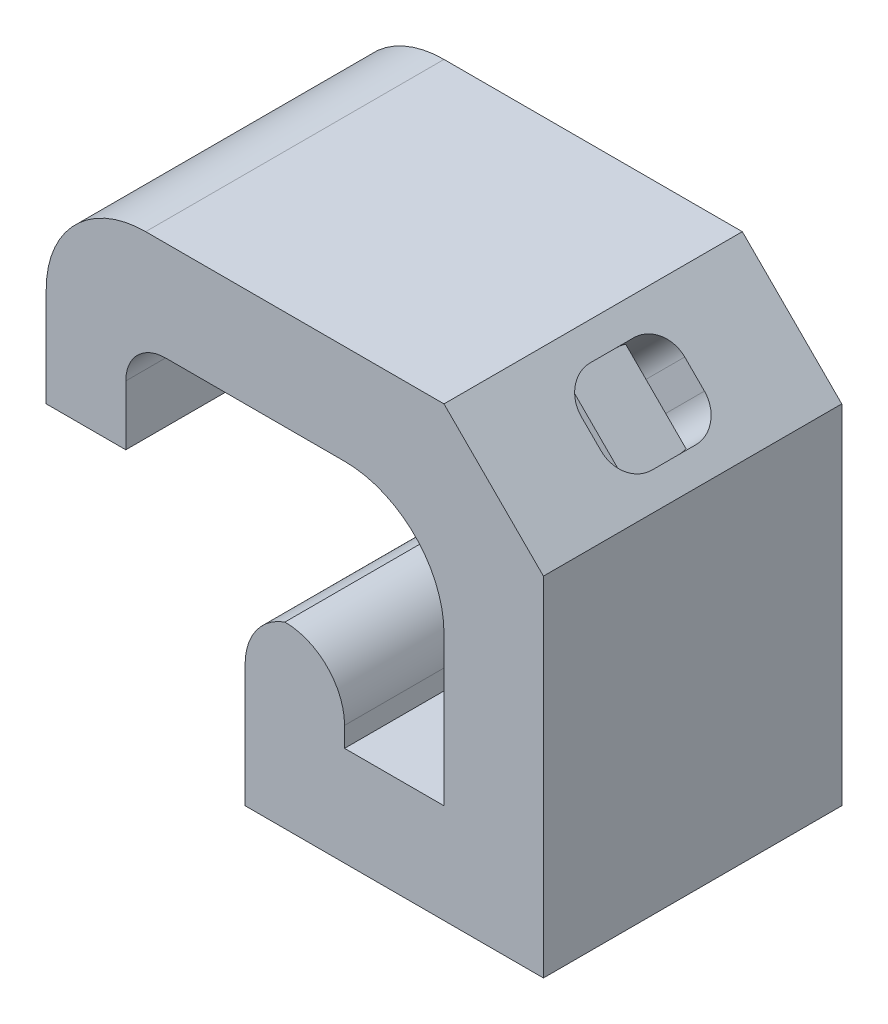
SolidWorks part; units mm, degrees
ref_plane "Front Plane" through (0, 0, 0) normal (0, 0, 1) x (1, 0, 0)
ref_plane "Top Plane" through (0, 0, 0) normal (0, 1, 0) x (1, 0, 0)
ref_plane "Right Plane" through (0, 0, 0) normal (1, 0, 0) x (0, 0, -1)
sketch "Sketch1" plane through (0, 0, 0) normal (0, 0, 1) x (1, 0, 0)
  line L0 (0, 0) -> (0, 4)
  line L1 (0, 0) -> (5, 0)
  line L3 (-11, 12.5) -> (5, 12.5)
  line L4 (5, 0) -> (5, 12.5)
  line L5 (0, 4) -> (-5, 4)
  line L6 (-11, 17.5) -> (5, 17.5)
  line L7 (10, -5) -> (10, 12.5)
  line L8 (-5, -5) -> (10, -5)
  line L9 (-5, -5) -> (-5, 4)
  line L10 (-5, -1) -> (-5, -1)
  line L11 (-5, -5) -> (-5, -1) construction
  line L13 (5, 17.5) -> (10, 12.5)
  line L14 (10, -5) -> (10, 17.5) construction
  line L15 (-11, 17.5) -> (10, 17.5) construction
  line L17 (-11, 17.5) -> (-15, 17.5)
  line L18 (-11, 12.5) -> (-11, 7.5)
  line L19 (-11, 7.5) -> (-15, 7.5)
  line L20 (-15, 17.5) -> (-15, 7.5)
  dimension "D1" = 5
  dimension "D2" = 12.5
  dimension "D3" = 16
  dimension "D4" = 4
  dimension "D5" = 5
  dimension "D6" = 45
  dimension "D7" = 4
  dimension "D8" = 10
extrude "Boss-Extrude1" add sketch "Sketch1" along normal blind 15 contours L3 L4 L1 L0 L5 L9 L8 L7 L13 L6 L17 L20 L19 L18
fillet "Fillet1" radius 5 1 edges at (5, 12.5, 7.5)
sketch "Sketch2" plane through (11.25, 11.25, 0) normal (0.7071, 0.7071, 0) x (0, 0, -1)
  line L0 (-7.5, 8.8388) -> (-7.5, 1.7678) construction
  line L1 (-15, 8.8388) -> (0, 8.8388) construction
  line L2 (-15, 1.7678) -> (0, 1.7678) construction
  line L3 (-9, 7.449) -> (-9, 3.1576)
  line L4 (-8.6, 7.5033) -> (-6.4, 7.5033)
  line L5 (-10.1, 6.0033) -> (-10.1, 4.6033)
  line L6 (-8.6, 3.1033) -> (-6.4, 3.1033)
  line L7 (-4.9, 6.0033) -> (-4.9, 4.6033)
  line L8 (-10.1, 7.5033) -> (-4.9, 3.1033) construction
  line L9 (-10.1, 3.1033) -> (-4.9, 7.5033) construction
  line L10 (-6, 7.449) -> (-6, 3.1576)
  line L11 (-9, 8.8388) -> (-9, 1.7678) construction
  line L12 (-6, 8.8388) -> (-6, 1.7678) construction
  arc A0 (-4.9, 6.0033) -> (-6.4, 7.5033) centre (-6.4, 6.0033) ccw
  arc A1 (-4.9, 4.6033) -> (-6.4, 3.1033) centre (-6.4, 4.6033) cw
  arc A2 (-8.6, 3.1033) -> (-10.1, 4.6033) centre (-8.6, 4.6033) cw
  arc A3 (-8.6, 7.5033) -> (-10.1, 6.0033) centre (-8.6, 6.0033) ccw
  point P6 (-7.5, 5.3033)
  dimension "D3" = 1.5
  dimension "D1" = 5.2
  dimension "D2" = 4.4
  dimension "D4" = 1.5
  dimension "D5" = 1.5
extrude "Cut-Extrude3" cut sketch "Sketch2" against normal blind 1.2 contours L4 A0 L7 A1 L6 A2 L5 A3
extrude "Cut-Extrude4" cut sketch "Sketch2<5>" against normal blind 10 and the other way through all contours L3 A3 L5 A2 | A1 L7 A0 L10 region at (7.5, 15, 9.4942) region at (7.5, 15, 5.5058)
sketch "Sketch2<5>" plane through (11.25, 11.25, 0) normal (0.7071, 0.7071, 0) x (0, 0, -1) same geometry as "Sketch2"
fillet "Fillet2" radius 3 1 edges at (0, 4, 7.5)
fillet "Fillet3" radius 3 1 edges at (-5, 4, 7.5)
fillet "Fillet4" radius 5 1 edges at (-15, 17.5, 7.5)
fillet "Fillet5" radius 2 1 edges at (-11, 12.5, 7.5)
